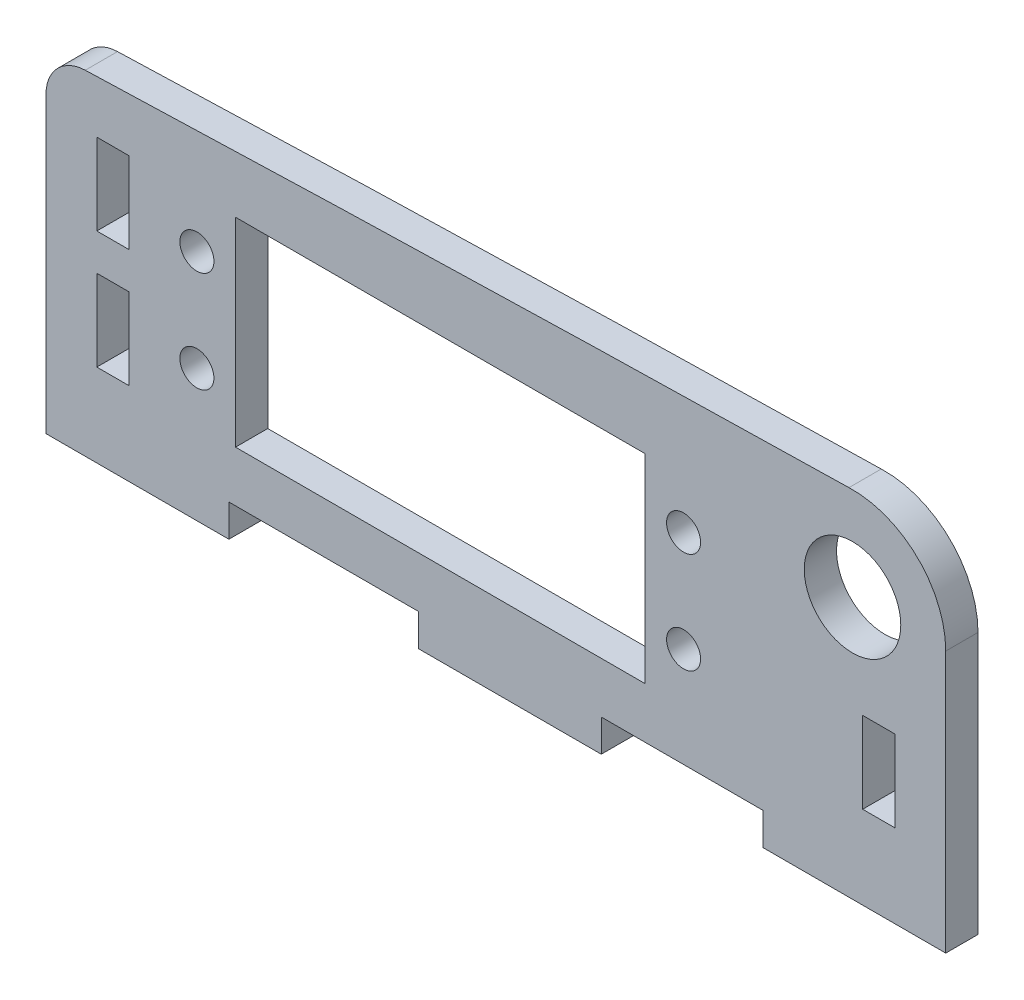
SolidWorks part; units mm, degrees
ref_plane "Front Plane" through (0, 0, 0) normal (0, 0, 1) x (1, 0, 0)
ref_plane "Top Plane" through (0, 0, 0) normal (0, 1, 0) x (1, 0, 0)
ref_plane "Right Plane" through (0, 0, 0) normal (1, 0, 0) x (0, 0, -1)
sketch "Sketch1" plane through (0, 0, 0) normal (0, 0, 1) x (1, 0, 0)
  line L1 (-26.416, -9.8) -> (26.416, -9.8)
  line L2 (-26.416, -9.8) -> (-26.416, 9.8)
  line L3 (-26.416, 9.8) -> (26.416, 9.8)
  line L4 (26.416, -9.8) -> (26.416, 9.8)
  line L5 (-26.416, -9.8) -> (26.416, 9.8) construction
  line L6 (-26.416, 9.8) -> (26.416, -9.8) construction
  line L7 (-20.15, -9.8) -> (20.15, -9.8)
  line L8 (-20.15, -9.8) -> (-20.15, 9.8)
  line L9 (-20.15, 9.8) -> (20.15, 9.8)
  line L10 (20.15, -9.8) -> (20.15, 9.8)
  line L11 (-20.15, -9.8) -> (20.15, 9.8) construction
  line L12 (-20.15, 9.8) -> (20.15, -9.8) construction
  line L13 (-26.416, 9.8) -> (26.416, 9.8)
  line L14 (-26.416, 9.8) -> (-26.416, 14.8)
  line L15 (-26.416, 14.8) -> (26.416, 14.8)
  line L16 (26.416, 9.8) -> (26.416, 14.8)
  line L17 (26.416, -9.8) -> (-26.416, -9.8)
  line L18 (26.416, -9.8) -> (26.416, -14.8)
  line L19 (26.416, -14.8) -> (-26.416, -14.8)
  line L20 (-26.416, -9.8) -> (-26.416, -14.8)
  circle A0 centre (-23.95, -4.974) radius 1.675
  circle A1 centre (-23.95, 4.974) radius 1.675
  circle A2 centre (23.95, 4.974) radius 1.675
  circle A3 centre (23.95, -4.974) radius 1.675
  point P0 (0, 0)
  point P14 (0, 0)
  dimension "D1" = 3.35
  dimension "D2" = 3.35
  dimension "D3" = 3.35
  dimension "D4" = 3.35
  dimension "D7" = 4.826
  dimension "D8" = 3.8
  dimension "D9" = 3.8
  dimension "D10" = 4.826
  dimension "D11" = 4.826
  dimension "D12" = 4.826
  dimension "D13" = 3.8
  dimension "D5" = 19.6
  dimension "D6" = 52.832
  dimension "D15" = 40.3
  dimension "D16" = 5
  dimension "D17" = 5
  dimension "3.9" = 3.8
extrude "Boss-Extrude2" add sketch "Sketch1" along normal blind 3.175 contours L1 L8 L3 L2 A1 A0 | L1 L20 L19 L18 | L3 L16 L15 L14 | L10 L1 L4 L3 A3 A2 | L14 L13 L16 L15 region at (-23.1712, 0, 0) region at (0, -12.3, 0) region at (0, 12.3, 0) region at (23.1712, 0, 0)
sketch "Sketch3" plane through (0, 0, 3.175) normal (0, 0, 1) x (1, 0, 0)
  line L0 (26.416, -14.8) -> (56.416, -14.8)
  line L6 (26.416, 14.8) -> (56.416, 14.8)
  line L7 (26.416, 14.8) -> (26.416, -14.906)
  line L8 (26.416, -14.906) -> (56.416, -14.906)
  line L9 (56.416, 14.8) -> (56.416, -14.906)
  line M3 (26.416, -14.8) -> (26.416, 14.8)
  dimension "D2" = 30
extrude "Boss-Extrude3" add sketch "Sketch3" against normal up to surface (3.175 mm away) contours L9 L6 L0 M3 region at (41.416, 0, 3.175) up to face at (0, 0, 0)
sketch "Sketch4" plane through (0, 0, 0) normal (0, 0, -1) x (-1, 0, 0)
  line L3 (-56.416, 14.8) -> (-56.416, -14.8) construction
  line L4 (-56.416, -14.8) -> (26.416, -14.8) construction
  circle A0 centre (-40.576, 7.77) radius 4.75
  dimension "D1" = 15.84
  dimension "D2" = 22.57
  dimension "D3" = 9.5
extrude "Cut-Extrude1" cut sketch "Sketch4" against normal blind 10 contours A0
sketch "Sketch22" plane through (0, 0, 0) normal (0, 0, -1) x (-1, 0, 0)
  line L0 (-52.3294, 14.8) -> (-30.0917, 14.8)
  line L1 (26.416, 14.8) -> (-56.416, 14.8) construction
  circle A0 centre (-40.576, 7.77) radius 9.175
  dimension "D1" = 18.35
extrude "Boss-Extrude14" add sketch "Sketch22" against normal up to surface (3.175 mm away) contours L0 A0 region at (40.576, 15.6672, 0) up to face at (45.326, 7.77, 3.175)
sketch "Sketch23" plane through (0, 0, 0) normal (0, 0, -1) x (-1, 0, 0)
  line L0 (-49.751, 7.77) -> (-49.751, -14.8)
  line L1 (-56.416, -14.8) -> (26.416, -14.8) construction
  circle A0 centre (-40.576, 7.77) radius 9.175
  line M4 (-46.4717, 14.8) -> (-56.416, 14.8)
  line M5 (-56.416, 14.8) -> (-56.416, -14.8)
  line M6 (-56.416, -14.8) -> (26.416, -14.8)
extrude "Cut-Extrude8" cut sketch "Sketch23" against normal blind 10 contours A0 L0 M4 M5 M6 region at (52.9363, 0.4514, 0)
sketch "Sketch24" plane through (0, 0, 0) normal (0, 0, -1) x (-1, 0, 0)
  line L0 (25.625, 4.974) -> (25.625, 17.1862)
  line L1 (21.4452, -14.8) -> (27.751, -14.8)
  line L2 (-49.751, -14.8) -> (26.416, -14.8) construction
  line L3 (26.416, 14.8) -> (-34.6803, 14.8) construction
  line L4 (25.625, 14.8) -> (30.625, 14.8)
  line L5 (25.625, 14.8) -> (25.625, -14.8)
  line L6 (25.625, -14.8) -> (30.625, -14.8)
  line L7 (30.625, 14.8) -> (30.625, -14.8)
  circle A0 centre (23.95, 4.974) radius 1.675 construction
  line M14 (26.416, -14.8) -> (26.416, 14.8)
  dimension "D1" = 5
extrude "Boss-Extrude15" add sketch "Sketch24" against normal up to surface (3.175 mm away) contours L7 L4 L1 L6 M14 region at (-28.5205, 0, 0) up to face at (45.326, 7.77, 3.175)
sketch "Sketch25" plane through (0, 0, 0) normal (0, 0, -1) x (-1, 0, 0)
  line L0 (30.625, 14.8) -> (30.625, -14.8) construction
  line L1 (30.625, 9.8) -> (33.8, 9.8)
  line L2 (30.625, 9.8) -> (30.625, 1.8)
  line L3 (30.625, 1.8) -> (33.8, 1.8)
  line L4 (33.8, 9.8) -> (33.8, 1.8)
  line L5 (28.9462, -14.8) -> (31.8791, -14.8)
  line L6 (30.625, -1.8) -> (33.8, -1.8)
  line L7 (30.625, -1.8) -> (30.625, -9.8)
  line L8 (30.625, -9.8) -> (33.8, -9.8)
  line L9 (33.8, -1.8) -> (33.8, -9.8)
  line L10 (-49.751, -14.8) -> (30.625, -14.8) construction
  line L12 (30.625, 14.8) -> (38.8, 14.8)
  line L13 (30.625, 14.8) -> (30.625, -14.8)
  line L14 (30.625, -14.8) -> (38.8, -14.8)
  line L15 (38.8, 14.8) -> (38.8, -14.8)
  line M23 (30.625, -14.8) -> (30.625, 14.8)
  dimension "D1" = 3.175
  dimension "D2" = 3.175
  dimension "D3" = 8
  dimension "D4" = 8
  dimension "D5" = 5
  dimension "D6" = 0
  dimension "D7" = 8.175
  dimension "D8" = 5
extrude "Boss-Extrude16" add sketch "Sketch25" against normal up to surface (3.175 mm away) contours L15 L12 L1 L4 L3 L6 L9 L8 L5 L14 M23 region at (-35.3768, 0, 0) up to face at (45.326, 7.77, 3.175)
sketch "Sketch26" plane through (0, 0, 0) normal (0, 0, -1) x (-1, 0, 0)
  line L0 (-34.6803, 14.8) -> (38.8, 14.8)
  arc A0 (-40.576, 16.945) -> (38.8, 14.8) centre (-135.5308, -4966.6007) cw
  arc A1 (-34.6803, 14.8) -> (-49.751, 7.77) centre (-40.576, 7.77) ccw construction
  circle A2 centre (-40.576, 7.77) radius 9.175
  arc M18 (-34.6803, 14.8) -> (-49.751, 7.77) centre (-40.576, 7.77) ccw
  line M22 (38.8, 14.8) -> (-34.6803, 14.8)
extrude "Boss-Extrude17" add sketch "Sketch26" against normal up to surface (3.175 mm away) contours A0 M18 M22 region at (10.3443, 15.541, 0) up to face at (-32.2125, 5.8, 3.175)
fillet "Fillet5" radius 4 1 edges at (-38.8, 14.8, 1.5875)
sketch "Sketch27" plane through (0, 0, 0) normal (0, 0, -1) x (-1, 0, 0)
  line L0 (-49.751, -14.8) -> (38.8, -14.8) construction
  line L1 (-44.751, -9.8) -> (-41.576, -9.8)
  line L2 (-44.751, -9.8) -> (-44.751, -1.8)
  line L3 (-44.751, -1.8) -> (-41.576, -1.8)
  line L4 (-41.576, -9.8) -> (-41.576, -1.8)
  line L5 (-49.751, 7.77) -> (-49.751, -14.8) construction
  dimension "D1" = 3.175
  dimension "D2" = 8
  dimension "D3" = 5
  dimension "D4" = 5
extrude "Cut-Extrude9" cut sketch "Sketch27" against normal blind 10
sketch "Sketch28" plane through (0, 0, 0) normal (0, 0, -1) x (-1, 0, 0)
  line L0 (-49.751, -14.8) -> (38.8, -14.8) construction
  line L1 (-49.751, -14.8) -> (-31.751, -14.8)
  line L2 (-49.751, -14.8) -> (-49.751, -17.975)
  line L3 (-49.751, -17.975) -> (-31.751, -17.975)
  line L4 (-31.751, -14.8) -> (-31.751, -17.975)
  line L5 (-15.85, -14.8) -> (2.15, -14.8)
  line L6 (-15.85, -14.8) -> (-15.85, -17.975)
  line L7 (-15.85, -17.975) -> (2.15, -17.975)
  line L8 (2.15, -14.8) -> (2.15, -17.975)
  line L9 (38.8, 10.936) -> (38.8, -14.8) construction
  line L10 (20.8, -14.8) -> (38.8, -14.8)
  line L11 (20.8, -14.8) -> (20.8, -17.975)
  line L12 (20.8, -17.975) -> (38.8, -17.975)
  line L13 (38.8, -14.8) -> (38.8, -17.975)
  dimension "D1" = 3.175
  dimension "D2" = 3.175
  dimension "D3" = 3.175
  dimension "D4" = 18
  dimension "D5" = 18
  dimension "D6" = 18
  dimension "D7" = 0
  dimension "D8" = 18.65
extrude "Boss-Extrude18" add sketch "Sketch28" against normal up to surface (3.175 mm away) contours L2 L1 L4 L3 | L6 L5 L8 L7 | L11 L10 L13 L12 up to face at (43.1635, -5.8, 3.175)
sketch "Sketch30" plane through (0, 0, 0) normal (0, 0, -1) x (-1, 0, 0)
  circle A0 centre (-40.576, 7.77) radius 4.75
